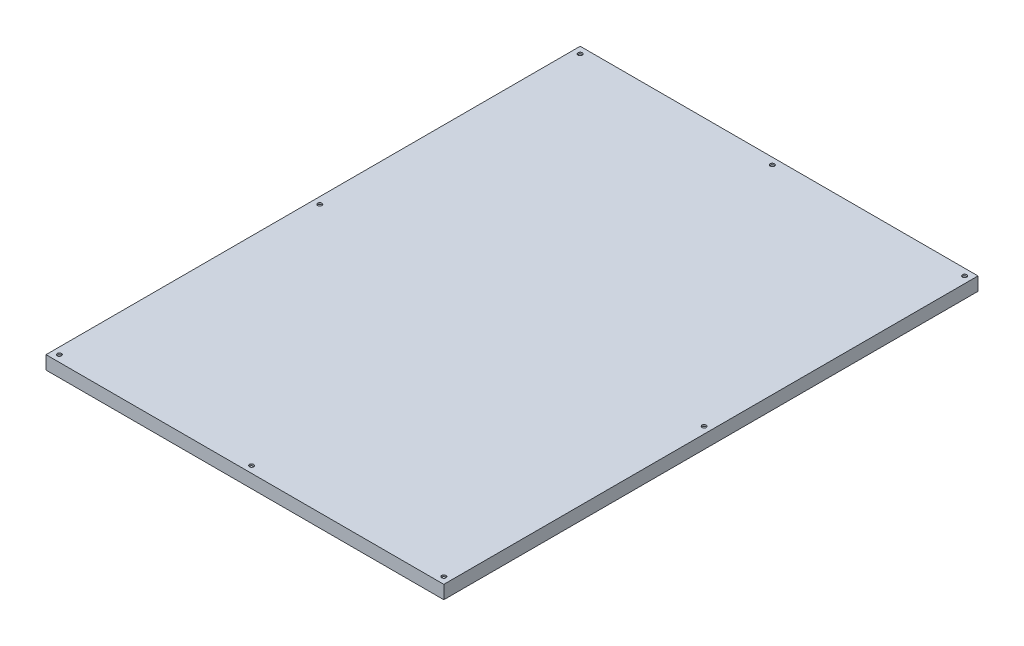
SolidWorks part; units mm, degrees
ref_plane "Front Plane" through (0, 0, 0) normal (0, 0, 1) x (1, 0, 0)
ref_plane "Top Plane" through (0, 0, 0) normal (0, 1, 0) x (1, 0, 0)
ref_plane "Right Plane" through (0, 0, 0) normal (1, 0, 0) x (0, 0, -1)
sketch "Sketch1" plane through (0, 0, 0) normal (0, 1, 0) x (1, 0, 0)
  line L1 (0, 0) -> (297.5, 0)
  line L2 (0, 0) -> (0, 399.5)
  line L3 (0, 399.5) -> (297.5, 399.5)
  line L4 (297.5, 0) -> (297.5, 399.5)
  dimension "D1" = 399.5
  dimension "D2" = 297.5
extrude "Boss-Extrude1" add sketch "Sketch1" along normal blind 10
sketch "Sketch2" plane through (0, 10, 0) normal (0, 1, 0) x (1, 0, 0)
  circle A0 centre (292.5, 199.75) radius 1.6 construction
  circle A1 centre (292.5, 5) radius 1.6 construction
  circle A2 centre (148.75, 5) radius 1.6 construction
  circle A3 centre (5, 5) radius 1.6 construction
  circle A4 centre (5, 199.75) radius 1.6 construction
  circle A5 centre (292.5, 394.5) radius 1.6 construction
  circle A6 centre (148.75, 394.5) radius 1.6 construction
  circle A7 centre (5, 394.5) radius 1.6 construction
  circle A8 centre (292.5, 199.75) radius 1.6
  circle A9 centre (292.5, 5) radius 1.6
  circle A10 centre (148.75, 5) radius 1.6
  circle A11 centre (5, 5) radius 1.6
  circle A12 centre (5, 199.75) radius 1.6
  circle A13 centre (292.5, 394.5) radius 1.6
  circle A14 centre (148.75, 394.5) radius 1.6
  circle A15 centre (5, 394.5) radius 1.6
extrude "Cut-Extrude1" cut sketch "Sketch2" against normal blind 1.2
